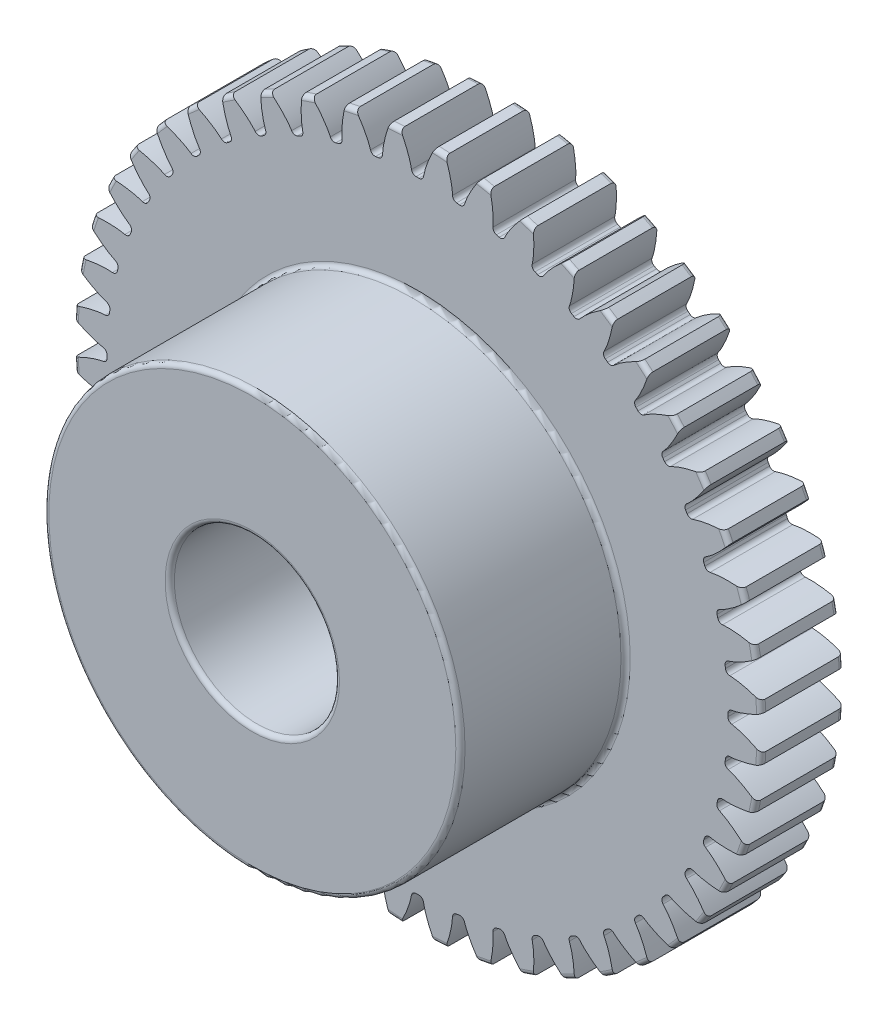
SolidWorks part; units mm, degrees
ref_plane "Front Plane" through (0, 0, 0) normal (0, 0, 1) x (1, 0, 0)
ref_plane "Top Plane" through (0, 0, 0) normal (0, 1, 0) x (1, 0, 0)
ref_plane "Right Plane" through (0, 0, 0) normal (1, 0, 0) x (0, 0, -1)
sketch "Sketch1" plane through (0, 0, 0) normal (0, 0, 1) x (1, 0, 0)
  line L0 (0, 0) -> (0, 12.7) construction
  line L1 (-4.0817, 14.1856) -> (4.0817, 11.2144) construction
  circle A0 centre (0, 0) radius 12.0385 construction
  circle A1 centre (0, 0) radius 13.2292 construction
  circle A2 centre (0, 0) radius 12.7 construction
  circle A3 centre (0, 0) radius 11.9341 construction
  circle A4 centre (0, 0) radius 3.175 construction
  circle A5 centre (0, 0) radius 8.001 construction
  point P8 (609.6, 0)
  point P13 (609.6, 0)
  dimension "OD | Outside Diameter" = 26.4583
  dimension "Root Diameter" = 24.0771
  dimension "Gear Pitch Diameter" = 25.4
  dimension "Base Diameter" = 23.8682
  dimension "For Shaft Diameter" = 6.35
  dimension "Hub Diameter" = 16.002
  dimension "Pressure Angle" = 20
  dimension "Number of Teeth" = 1219.2
  dimension "Gear Pitch | Diametral Pitch" = 1219.2
sketch "Sketch2" plane through (0, 0, 0) normal (1, 0, 0) x (0, 0, -1)
  line L0 (-4.7625, 0) -> (4.7625, 0) construction
  line L1 (-4.7625, 13.2292) -> (4.7625, 13.2292) construction
  point P2 (0, 13.2292)
  point P4 (1.5875, 0)
  point P6 (1.5875, 13.2292)
  dimension "Overall Width" = 9.525
  dimension "Hub Width" = 6.35
  dimension "Face Width" = 3.175
sketch "Sketch3" plane through (0, 0, 0) normal (0, 0, 1) x (1, 0, 0)
  circle A0 centre (0, 0) radius 13.2292
  circle A1 centre (0, 0) radius 13.2292 construction
extrude "Boss-Extrude1" add sketch "Sketch3" against normal up to vertex (4.7625 mm away) and the other way up to vertex (4.7625 mm away) up to point (0, 0, -4.7625) other way up to point (0, 0, 4.7625)
sketch "Sketch5" plane through (0, 0, 0) normal (1, 0, 0) x (0, 0, -1)
  line L1 (-4.7625, 13.2292) -> (1.5875, 13.2292)
  line L2 (-4.7625, 13.2292) -> (-4.7625, 8.001)
  line L3 (-4.7625, 8.001) -> (1.5875, 8.001)
  line L4 (1.5875, 13.2292) -> (1.5875, 8.001)
  line L11 (4.7625, 3.175) -> (-4.7625, 3.175)
  line L12 (4.7625, 3.175) -> (4.7625, 0)
  line L13 (4.7625, 0) -> (-4.7625, 0)
  line L14 (-4.7625, 3.175) -> (-4.7625, 0)
  point P5 (0, 3.175)
  point P12 (0, 8.001)
revolve "Cut-Revolve1" cut sketch "Sketch5" angle 360 about L0
fillet "Fillet2" radius 0.1775 6 edges at (13.2292, 0, -4.7625) (3.175, 0, -4.7625) (3.175, 0, 4.7625) (8.001, 0, -1.5875) (13.2292, 0, -1.5875) (8.001, 0, 4.7625)
sketch "Sketch4" plane through (0, 0, 0) normal (0, 0, 1) x (1, 0, 0)
  line L0 (0, 0) -> (11.9321, 0.2127) construction
  line L2 (0, 0) -> (11.9321, -0.2127) construction
  line L4 (11.9321, 0.2127) -> (11.9322, 0.2127)
  line L5 (11.9322, -0.2127) -> (11.9321, -0.2127)
  arc A0 (11.9321, 0.2127) -> (11.9321, -0.2127) centre (0, 0) cw
  arc A3 (13.2126, 0.6611) -> (13.2126, -0.6611) centre (0, 0) cw
  circle A4 centre (0, 0) radius 13.2292 construction
  spline S0 degree 4 poles (11.9322, 0.2127) (11.9342, 0.2127) (11.9399, 0.2129) (11.9506, 0.2136) (11.968, 0.2151) (11.9902, 0.2174) (12.0189, 0.2211) (12.0527, 0.2262) (12.0898, 0.2325) (12.1301, 0.2404) (12.1703, 0.2489) (12.2103, 0.2582) (12.2502, 0.2681) (12.2985, 0.2808) (12.3563, 0.2972) (12.4237, 0.3179) (12.5002, 0.3431) (12.5779, 0.3708) (12.6543, 0.3997) (12.7314, 0.4308) (12.8058, 0.4621) (12.883, 0.4966) (12.9542, 0.5294) (13.0337, 0.5682) (13.0979, 0.6002) (13.1824, 0.6446) (13.2322, 0.6715) (13.2904, 0.7038) (13.3162, 0.7185) (13.3321, 0.7276) knots 0 0 0 0 0 0.005377 0.015084 0.028532 0.04661 0.064855 0.092111 0.119476 0.146842 0.174209 0.201575 0.228941 0.256307 0.307035 0.361767 0.4165 0.471232 0.525964 0.580697 0.635429 0.690161 0.744894 0.799626 0.854358 0.909091 0.954545 1 1 1 1 1 construction
  spline S1 degree 4 poles (11.9322, 0.2127) (11.9342, 0.2127) (11.9399, 0.2129) (11.9506, 0.2136) (11.968, 0.2151) (11.9902, 0.2174) (12.0189, 0.2211) (12.0527, 0.2262) (12.0898, 0.2325) (12.1301, 0.2404) (12.1703, 0.2489) (12.2103, 0.2582) (12.2502, 0.2681) (12.2985, 0.2808) (12.3563, 0.2972) (12.4237, 0.3179) (12.5002, 0.3431) (12.5779, 0.3708) (12.6543, 0.3997) (12.7314, 0.4308) (12.8058, 0.4621) (12.883, 0.4966) (12.9542, 0.5294) (13.0337, 0.5682) (13.0979, 0.6002) (13.164, 0.635) (13.1962, 0.6522) (13.2126, 0.6611) knots 0 0 0 0 0 0.005377 0.015084 0.028532 0.04661 0.064855 0.092111 0.119476 0.146842 0.174209 0.201575 0.228941 0.256307 0.307035 0.361767 0.4165 0.471232 0.525964 0.580697 0.635429 0.690161 0.744894 0.799626 0.854358 0.909091 0.909091 0.909091 0.909091 0.909091
  spline S2 degree 4 poles (11.9322, -0.2127) (11.9342, -0.2127) (11.9399, -0.2129) (11.9506, -0.2136) (11.968, -0.2151) (11.9902, -0.2174) (12.0189, -0.2211) (12.0527, -0.2262) (12.0898, -0.2325) (12.1301, -0.2404) (12.1703, -0.2489) (12.2103, -0.2582) (12.2502, -0.2681) (12.2985, -0.2808) (12.3563, -0.2972) (12.4237, -0.3179) (12.5002, -0.3431) (12.5779, -0.3708) (12.6543, -0.3997) (12.7314, -0.4308) (12.8058, -0.4621) (12.883, -0.4966) (12.9542, -0.5294) (13.0337, -0.5682) (13.0979, -0.6002) (13.1824, -0.6446) (13.2322, -0.6715) (13.2904, -0.7038) (13.3162, -0.7185) (13.3321, -0.7276) knots 0 0 0 0 0 0.005377 0.015084 0.028532 0.04661 0.064855 0.092111 0.119476 0.146842 0.174209 0.201575 0.228941 0.256307 0.307035 0.361767 0.4165 0.471232 0.525964 0.580697 0.635429 0.690161 0.744894 0.799626 0.854358 0.909091 0.954545 1 1 1 1 1 construction
  spline S3 degree 4 poles (11.9322, -0.2127) (11.9342, -0.2127) (11.9399, -0.2129) (11.9506, -0.2136) (11.968, -0.2151) (11.9902, -0.2174) (12.0189, -0.2211) (12.0527, -0.2262) (12.0898, -0.2325) (12.1301, -0.2404) (12.1703, -0.2489) (12.2103, -0.2582) (12.2502, -0.2681) (12.2985, -0.2808) (12.3563, -0.2972) (12.4237, -0.3179) (12.5002, -0.3431) (12.5779, -0.3708) (12.6543, -0.3997) (12.7314, -0.4308) (12.8058, -0.4621) (12.883, -0.4966) (12.9542, -0.5294) (13.0337, -0.5682) (13.0979, -0.6002) (13.164, -0.635) (13.1962, -0.6522) (13.2126, -0.6611) knots 0 0 0 0 0 0.005377 0.015084 0.028532 0.04661 0.064855 0.092111 0.119476 0.146842 0.174209 0.201575 0.228941 0.256307 0.307035 0.361767 0.4165 0.471232 0.525964 0.580697 0.635429 0.690161 0.744894 0.799626 0.854358 0.909091 0.909091 0.909091 0.909091 0.909091
  dimension "D1" = 23.8679
extrude "Cut-Extrude1" cut sketch "Sketch4" against normal through all both and the other way through all
fillet "Fillet1" radius 0.1775 2 edges at (11.9321, -0.2127, -3.175) (11.9321, 0.2127, -3.175)
pattern_circular "CirPattern1" count 48 over 360 about axis through (0, 0, 4.7625) along (0, 0, -1) of "Cut-Extrude1", "Fillet1"
equation "\"Root Diameter@Sketch1\"=\"Root Diameter\""
equation "\"OD | Outside Diameter@Sketch1\"=\"Outside Diameter\""
equation "\"D1@CirPattern1\"=\"Number of Teeth\""
equation "\"Diametral Pitch\"= 48"
equation "\"Number of Teeth\"= 48"
equation "\"Pressure Angle\"=20"
equation "\"Pitch Diameter\"= \"Number of Teeth\" / \"Diametral Pitch\""
equation "\"Base Diameter\"= \"Pitch Diameter\" * cos ( \"Pressure Angle\" )"
equation "\"Outside Diameter\"= ( \"Number of Teeth\" + 2 ) / \"Diametral Pitch\""
equation "\"Dedendum\"= 1.25 / \"Diametral Pitch\""
equation "\"Root Diameter\"= \"Pitch Diameter\" - ( 2 * \"Dedendum\" )"
equation "\"Pitch Angle\"= 360deg / \"Number of Teeth\""
equation "\"Alpha\"= sqr ( \"Pitch Diameter\" ^ 2 - \"Base Diameter\" ^ 2 ) / \"Base Diameter\" * 180 / PI - \"Pressure Angle\""
equation "\"Beta\"= ( \"Pitch Angle\" / 4 - \"Alpha\" )"
equation "\"Phi\"= sqr ( ( \"Outside Diameter\" / 2 ) ^ 2 - ( \"Base Diameter\" / 2 ) ^ 2 ) / ( \"Base Diameter\" / 2 )"
equation "\"Addendum\"= 1 / \"Diametral Pitch\""
equation "\"WorkingDepth\"= 2 / \"Diametral Pitch\""
equation "\"WholeDepth\"= 2.25 / \"Diametral Pitch\""
equation "\"Clearance\"= 0.25 / \"Diametral Pitch\""
equation "\"ToothThickness\"= ( pi * 2 ) / \"Diametral Pitch\""
equation "\"CircularPitch\"= pi / \"Diametral Pitch\""
equation "\"Number of Teeth@Sketch1\"=\"Number of Teeth\""
equation "\"Gear Pitch | Diametral Pitch@Sketch1\"=\"Diametral Pitch\""
equation "\"Pressure Angle@Sketch1\"=\"Pressure Angle\""
equation "\"Gear Pitch Diameter@Sketch1\"=\"Pitch Diameter\""
equation "\"Base Diameter@Sketch1\"=\"Base Diameter\""
equation "\"Fillet\"= \"Clearance\" * cos ( \"Pressure Angle\" ) * tan ( ( 90 + \"Pressure Angle\" ) / 2 )"
equation "\"D1@Fillet1\"=\"Fillet\""
equation "\"D1@Sketch4\"=if( \"Base Diameter\">\"Root Diameter\",\"Root Diameter\",\"Base Diameter\"-.00001)"
equation "\"D1@Fillet2\"=\"Fillet\""
